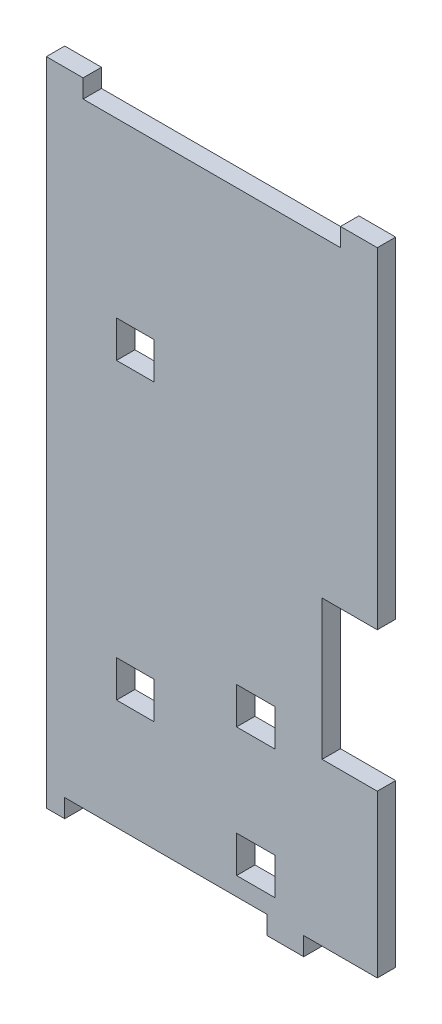
SolidWorks part; units mm, degrees
ref_plane "Plan de face" through (0, 0, 0) normal (0, 0, 1) x (1, 0, 0)
ref_plane "Plan de dessus" through (0, 0, 0) normal (0, 1, 0) x (1, 0, 0)
ref_plane "Plan de droite" through (0, 0, 0) normal (1, 0, 0) x (0, 0, -1)
sketch "Esquisse1" plane through (0, 0, 0) normal (0, 0, 1) x (1, 0, 0)
  line L0 (90, 82) -> (90, 167)
  line L1 (5, 0) -> (60, 0)
  line L2 (0, 0) -> (0, 167)
  line L3 (10, 167) -> (80, 167)
  line L4 (90, 0) -> (90, 44)
  line L5 (90, 82) -> (75, 82)
  line L6 (0, 167) -> (0, 172)
  line L7 (0, 172) -> (10, 172)
  line L8 (10, 167) -> (10, 172)
  line L9 (0, 0) -> (0, -5)
  line L10 (90, 167) -> (90, 172)
  line L11 (90, 172) -> (80, 172)
  line L12 (80, 167) -> (80, 172)
  line L13 (0, -5) -> (5, -5)
  line L14 (5, 0) -> (5, -5)
  line L16 (90, 44) -> (75, 44)
  line L17 (75, 82) -> (75, 44)
  line L18 (51.7344, 50) -> (62.2003, 50)
  line L19 (51.7344, 50) -> (51.7344, 40)
  line L20 (51.7344, 40) -> (62.2003, 40)
  line L25 (62.2003, 50) -> (62.2003, 40)
  line L32 (51.7344, 15) -> (62.2003, 15)
  line L34 (51.7344, 15) -> (51.7344, 5)
  line L35 (51.7344, 5) -> (62.2003, 5)
  line L37 (62.2003, 15) -> (62.2003, 5)
  line L45 (29.3073, 120) -> (19.0901, 120)
  line L46 (29.3073, 120) -> (29.3073, 110)
  line L47 (29.3073, 110) -> (19.0901, 110)
  line L48 (19.0901, 120) -> (19.0901, 110)
  line L53 (29.3073, 110) -> (29.3073, 120) construction
  line L54 (29.3073, 40) -> (19.0901, 40)
  line L55 (29.3073, 40) -> (29.3073, 30)
  line L56 (29.3073, 30) -> (19.0901, 30)
  line L57 (19.0901, 40) -> (19.0901, 30)
  line L58 (70, 0) -> (90, 0)
  line L60 (60, 0) -> (60, -5)
  line L61 (60, -5) -> (70, -5)
  line L62 (70, 0) -> (70, -5)
  dimension "D1" = 167
  dimension "D2" = 90
  dimension "D3" = 10
  dimension "D4" = 5
  dimension "D5" = 5
  dimension "D6" = 15
  dimension "D7" = 38
  dimension "D8" = 82
  dimension "D9" = 2
  dimension "D10" = 70
  dimension "D11" = 10
  dimension "D12" = 20
extrude "Boss.-Extru.1" add sketch "Esquisse1" along normal blind 5
